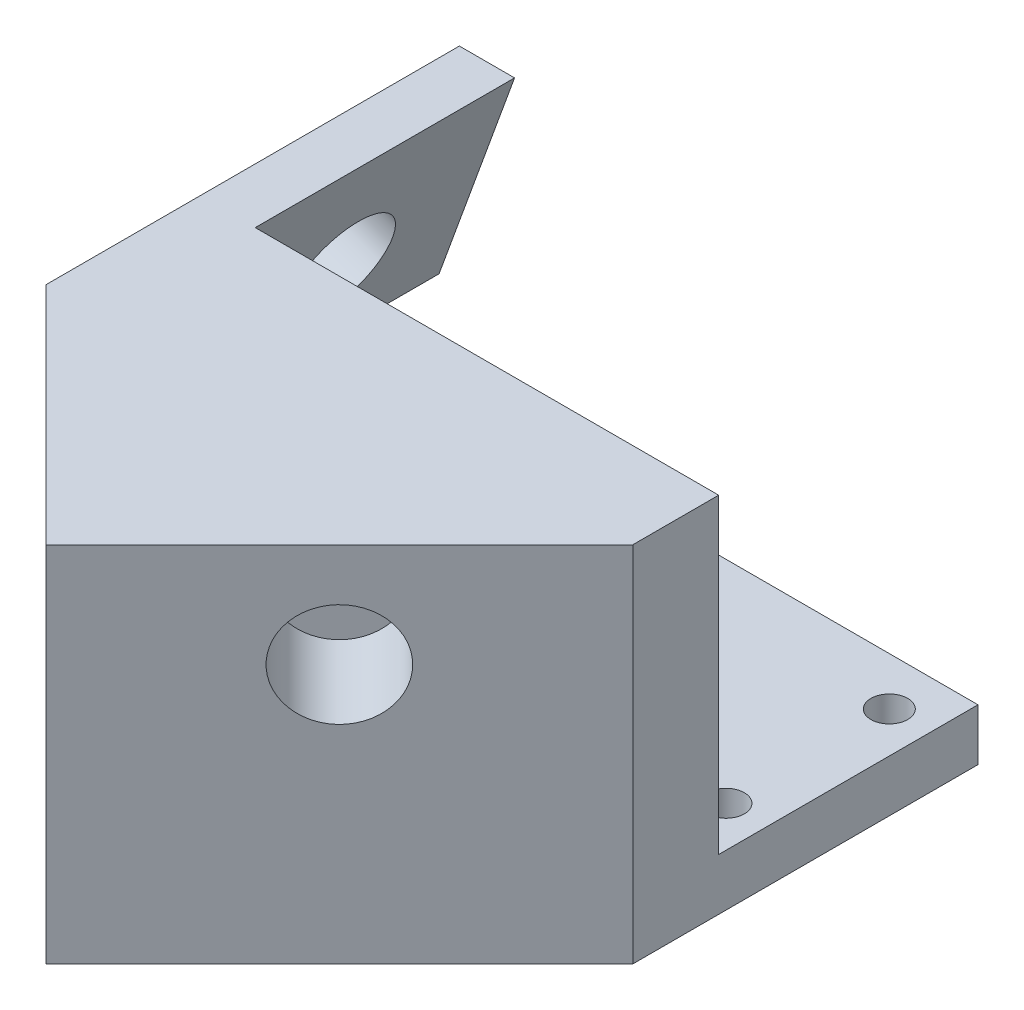
SolidWorks part; units mm, degrees
ref_plane "Front Plane" through (0, 0, 0) normal (0, 0, 1) x (1, 0, 0)
ref_plane "Top Plane" through (0, 0, 0) normal (0, 1, 0) x (1, 0, 0)
ref_plane "Right Plane" through (0, 0, 0) normal (1, 0, 0) x (0, 0, -1)
sketch "Sketch1" plane through (0, 0, 0) normal (0, 1, 0) x (1, 0, 0)
  line L0 (-35.921, 0) -> (0, 35.921)
  line L1 (-35.921, 0) -> (0, -35.921)
  line L2 (0, 35.921) -> (35.921, 0)
  line L3 (0, -35.921) -> (35.921, 0)
  line L4 (-35.921, 0) -> (35.921, 0) construction
  line L5 (0, 35.921) -> (0, -35.921) construction
  point P1 (0, 0)
  dimension "D1" = 50.8
  dimension "D2" = 50.8
extrude "Boss-Extrude1" add sketch "Sketch1" along normal mid plane 25.4
sketch "Sketch2" plane through (17.9605, 0, 17.9605) normal (0.7071, 0, 0.7071) x (0.7071, 0, -0.7071)
  circle A0 centre (0, 0) radius 6.35
  dimension "D1" = 12.7
extrude "Cut-Extrude1" cut sketch "Sketch2" against normal blind 12.7
sketch "Sketch3" plane through (-17.9605, 0, 17.9605) normal (-0.7071, 0, 0.7071) x (0.7071, 0, 0.7071)
  circle A0 centre (0, 0) radius 6.35
  dimension "D1" = 12.7
extrude "Cut-Extrude2" cut sketch "Sketch3" against normal blind 12.7
sketch "Sketch4" plane through (0, 12.7, 0) normal (0, 1, 0) x (1, 0, 0)
  line L0 (25.4, 10.521) -> (-25.4, 10.521)
  line L1 (35.921, 0) -> (0, 35.921) construction
  line L2 (0, 35.921) -> (-35.921, 0) construction
  line L3 (-25.4, 10.521) -> (0, 35.921)
  line L4 (0, 35.921) -> (25.4, 10.521)
  dimension "D1" = 25.4
extrude "Cut-Extrude3" cut sketch "Sketch4" against normal through all
sketch "Sketch5" plane through (0, 0, -10.521) normal (0, 0, -1) x (-1, 0, 0)
  line L0 (-35.921, 12.7) -> (-35.921, -12.7)
  line L1 (-35.921, -12.7) -> (36.8238, -12.7)
  line L2 (36.8238, -12.7) -> (27.579, 12.7)
  line L3 (27.579, 12.7) -> (-35.921, 12.7)
  line L4 (25.4, -12.7) -> (-25.4, -12.7) construction
  line L5 (-35.921, 12.7) -> (-35.921, -12.7) construction
  line L8 (25.4, 12.7) -> (-25.4, 12.7) construction
  point P6 (0, 0)
  dimension "D1" = 70
  dimension "D2" = 63.5
extrude "Boss-Extrude2" add sketch "Sketch5" against normal up to surface and the other way blind 31.75 up to face at (30.6605, 0, -5.2605)
sketch "Sketch6" plane through (-28.4345, 10.3493, 0) normal (-0.9397, 0.342, 0) x (0, 0, 1)
  line L0 (-42.271, -24.5286) -> (-42.271, 2.5015) construction
  line L1 (-42.271, -24.5286) -> (-10.521, -24.5286) construction
  circle A0 centre (-26.396, -11.0135) radius 6.35
  point P4 (-42.271, -11.0135)
  point P7 (-26.396, -24.5286)
  dimension "D1" = 12.7
extrude "Cut-Extrude4" cut sketch "Sketch6" against normal through all
sketch "Sketch7" plane through (0, 0, -42.271) normal (0, 0, -1) x (-1, 0, 0)
  line L1 (-35.921, -12.7) -> (36.8238, -12.7) construction
  line L3 (20.8214, 12.7) -> (30.0663, -12.7)
  line L4 (-35.921, -12.7) -> (30.0663, -12.7)
  line L5 (36.8238, -12.7) -> (27.579, 12.7) construction
  line L6 (27.579, 12.7) -> (-35.921, 12.7) construction
  line L7 (-35.921, -12.7) -> (-35.921, 12.7)
  line L8 (-35.921, 12.7) -> (20.8214, 12.7)
  dimension "D3" = 6.35
extrude "Cut-Extrude5" cut sketch "Sketch7" against normal blind 31.75
sketch "Sketch8" plane through (0, 12.7, 0) normal (0, 1, 0) x (1, 0, 0)
  line L5 (-42.1413, -6.2203) -> (-8.2965, -39.8855)
  line L6 (0, -35.921) -> (0, -57.0039)
  line L13 (0, -57.0039) -> (-46.5861, -10.6651)
  line L14 (-46.5861, -10.6651) -> (-42.1413, -6.2203)
  line L15 (-8.2965, -39.8855) -> (-8.2965, -27.6245)
  line L16 (-35.921, 0) -> (0, -35.921) construction
  line L17 (-8.2965, -27.6245) -> (0, -35.921)
  line L18 (-25.4, 10.521) -> (-35.921, 0) construction
extrude "Boss-Extrude3" [suppressed] add sketch "Sketch8" against normal up to surface (25.4 mm away) up to face at (2.1042, -12.7, 2.9758)
sketch "Sketch9" plane through (0, -12.7, 0) normal (0, -1, 0) x (1, 0, 0)
  line L0 (-25.4, -10.521) -> (-35.921, 0)
  line L1 (-35.921, 0) -> (-46.442, -10.521)
  line L2 (-46.442, -10.521) -> (-25.4, -10.521)
  line L3 (-35.921, 0) -> (0, 35.921) construction
extrude "Boss-Extrude4" add sketch "Sketch9" against normal up to surface (25.4 mm away) up to face at (-9.5866, 12.7, -10.0783)
sketch "Sketch10" plane through (0, 0, -42.271) normal (0, 0, -1) x (-1, 0, 0)
  line L0 (36.8238, -12.7) -> (27.579, 12.7) construction
  line L1 (36.8238, -12.7) -> (27.579, 12.7)
  line L6 (27.579, 12.7) -> (36.8238, -12.7)
  line L7 (36.8238, -12.7) -> (46.442, -12.7)
  line L8 (46.442, -12.7) -> (46.442, 12.7)
  line L9 (46.442, 12.7) -> (27.579, 12.7)
  line L10 (27.579, 12.7) -> (36.8238, -12.7)
  line L11 (36.8238, -12.7) -> (46.442, -12.7)
  line L12 (46.442, -12.7) -> (46.442, 12.7)
  line L13 (46.442, 12.7) -> (27.579, 12.7)
  line M7 (36.8238, -12.7) -> (27.579, 12.7)
  dimension "D1" = 0
extrude "Cut-Extrude6" cut sketch "Sketch10" against normal through all contours L12 L13 L11 M7 region at (-39.0717, 1.3741, -42.271)
sketch "Sketch11" plane through (0, -12.7, 0) normal (0, -1, 0) x (1, 0, 0)
  line L0 (-30.0663, -10.521) -> (-36.8238, -10.521)
  line L1 (-36.8238, -42.271) -> (-36.8238, -0.9028) construction
  line L2 (-36.8238, -10.521) -> (-36.8238, -0.9028)
  line L7 (0, 35.921) -> (-36.8238, -0.9028)
  line L8 (-36.8238, -0.9028) -> (-36.8238, -42.271)
  line L9 (-36.8238, -42.271) -> (-30.0663, -42.271)
  line L10 (-30.0663, -42.271) -> (-30.0663, -10.521)
  line L11 (-30.0663, -10.521) -> (35.921, -10.521)
  line L12 (35.921, -10.521) -> (35.921, 0)
  line L13 (35.921, 0) -> (0, 35.921)
  line L14 (0, 35.921) -> (-36.8238, -0.9028)
  line L18 (-30.0663, -10.521) -> (35.921, -10.521)
  line L19 (35.921, -10.521) -> (35.921, 0)
  line L20 (35.921, 0) -> (0, 35.921)
  dimension "D1" = 0
extrude "Boss-Extrude5" add sketch "Sketch11" along normal blind 12.7
sketch "Sketch12" plane through (0, -25.4, 0) normal (0, -1, 0) x (1, 0, 0)
  line L0 (35.921, -10.521) -> (35.921, 0)
  line L1 (35.921, 0) -> (0, 35.921)
  line L2 (0, 35.921) -> (-36.8238, -0.9028)
  line L3 (-36.8238, -0.9028) -> (-36.8238, -42.271)
  line L4 (-36.8238, -42.271) -> (35.921, -42.271)
  line L5 (35.921, -42.271) -> (35.921, -10.521)
  point P10 (0, 0)
  point P13 (-36.8238, -0.9028)
extrude "Boss-Extrude6" add sketch "Sketch12" along normal blind 6.35
sketch "Sketch14" plane through (0, 0, -10.521) normal (0, 0, -1) x (-1, 0, 0)
  line L0 (34.6887, -25.4) -> (20.8214, 12.7)
  line L1 (36.8238, -31.75) -> (26.3581, -31.75)
  line L2 (20.8214, 12.7) -> (10.1797, 12.7)
  line L3 (24.0469, -25.4) -> (10.1797, 12.7)
  line L4 (20.8214, 12.7) -> (-35.921, 12.7) construction
  line L5 (30.0663, -12.7) -> (20.8214, 12.7) construction
  line L6 (36.8238, -31.75) -> (-35.921, -31.75) construction
  line L7 (36.8238, -31.75) -> (36.8238, -25.4)
  line L8 (36.8238, -25.4) -> (34.6887, -25.4)
  line L9 (24.0469, -25.4) -> (24.0469, -31.75)
  line L10 (24.0469, -31.75) -> (26.3581, -31.75)
  line L11 (36.8238, -25.4) -> (-35.921, -25.4) construction
  point P10 (23.5069, -23.9162)
  dimension "D1" = 10
extrude "Cut-Extrude7" cut sketch "Sketch14" along normal through all
sketch "Sketch15" plane through (0, -31.75, 0) normal (0, -1, 0) x (1, 0, 0)
  line L0 (-24.0469, -42.271) -> (35.921, -42.271) construction
  line L1 (30.937, -16.396) -> (-19.063, -16.396) construction
  line L2 (30.937, -16.396) -> (30.937, -36.396) construction
  line L3 (30.937, -36.396) -> (-19.063, -36.396) construction
  line L4 (-19.063, -16.396) -> (-19.063, -36.396) construction
  line L5 (30.937, -16.396) -> (-19.063, -36.396) construction
  line L6 (30.937, -36.396) -> (-19.063, -16.396) construction
  line L9 (-24.0469, -42.271) -> (-24.0469, -10.521) construction
  circle A0 centre (30.937, -36.396) radius 2.25
  circle A1 centre (30.937, -16.396) radius 2.25
  circle A2 centre (-19.063, -16.396) radius 2.25
  circle A3 centre (-19.063, -36.396) radius 2.25
  point P0 (5.937, -26.396)
  point P11 (5.937, -42.271)
  point P14 (-24.0469, -26.396)
  dimension "D1" = 4.5
  dimension "D2" = 50
  dimension "D3" = 20
extrude "Cut-Extrude8" cut sketch "Sketch15" against normal up to next
